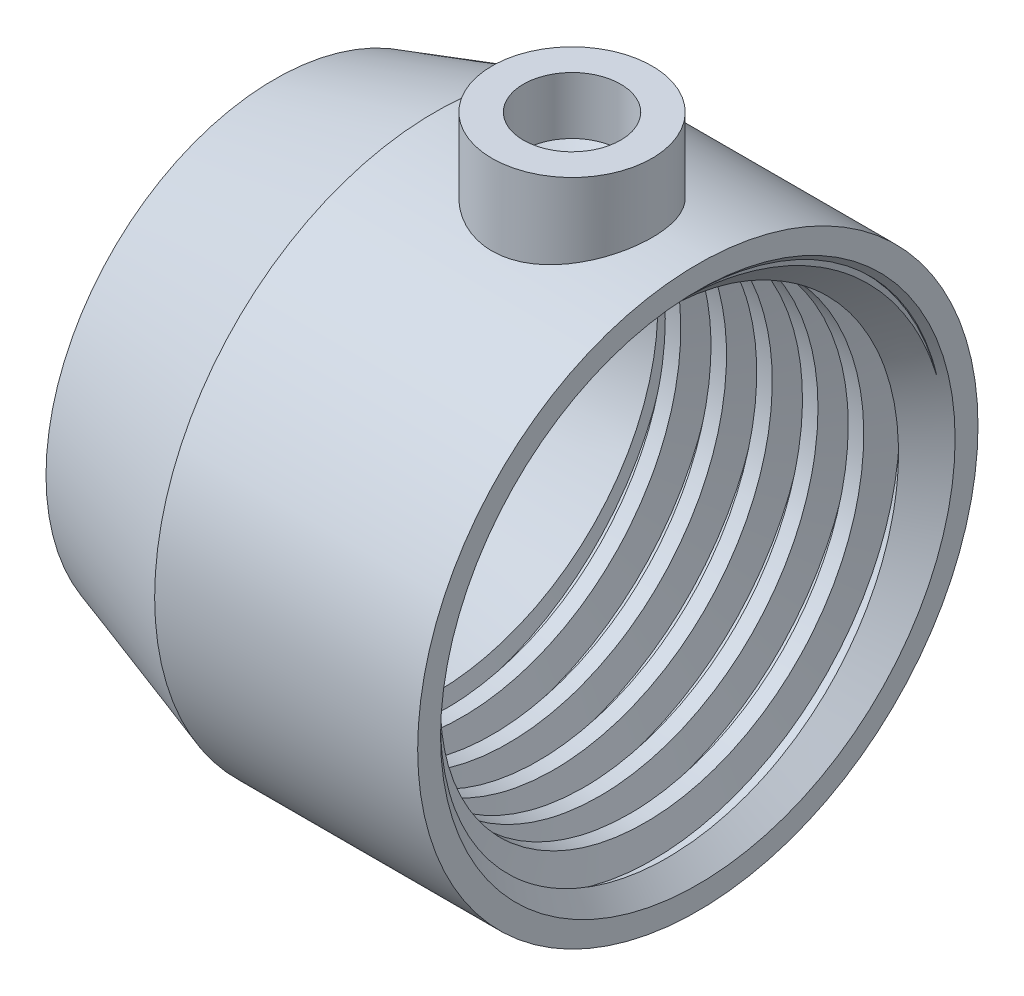
SolidWorks part; units mm, degrees
ref_plane "Front Plane" through (0, 0, 0) normal (0, 0, 1) x (1, 0, 0)
ref_plane "Top Plane" through (0, 0, 0) normal (0, 1, 0) x (1, 0, 0)
ref_plane "Right Plane" through (0, 0, 0) normal (1, 0, 0) x (0, 0, -1)
sketch "Sketch1" plane through (0, 0, 0) normal (0, 0, 1) x (1, 0, 0)
  line L0 (0, 0) -> (39.5756, 0) construction
  line L1 (0, 13.5) -> (0, 20)
  line L2 (0, 20) -> (14, 24.5)
  line L3 (14, 24.5) -> (37, 24.5)
  line L4 (37, 24.5) -> (37, 19.5)
  line L5 (37, 19.5) -> (14, 19.5)
  line L6 (14, 19.5) -> (3, 15.9643)
  line L7 (3, 15.9643) -> (3, 13.5)
  line L8 (3, 13.5) -> (0, 13.5)
  dimension "D1" = 37
  dimension "D2" = 13.5
  dimension "D3" = 19.5
  dimension "D4" = 24.5
  dimension "D5" = 20
  dimension "D6" = 13.5
  dimension "D7" = 3
  dimension "D8" = 11
revolve "Revolve1" add sketch "Sketch1" angle 360 about L0
chamfer "Chamfer1" distance 3 angle 45 1 edges at (37, 0, 19.5)
sketch "Sketch2" plane through (37, 0, 0) normal (1, 0, 0) x (0, 0, -1)
  circle A0 centre (0, 0) radius 19.5 construction
  circle A1 centre (0, 0) radius 19.5
curve "Helix/Spiral1" pitch 4 height 23 turns 5.75
sketch "Sketch4" plane through (0, 0, 0) normal (0, 0, 1) x (1, 0, 0)
  line L0 (37, -19.5) -> (39.6431, -19.5)
  line L1 (37, -24.5) -> (37, 24.5) construction
  line L2 (39.6431, -19.5) -> (38.9965, -22)
  line L3 (38.9965, -22) -> (37.6465, -22)
  line L4 (37.6465, -22) -> (37, -19.5)
  line L5 (38.3215, -19.5) -> (38.3215, -22.5962) construction
  spline S0 degree 3 poles (37, -19.5) (36.9318, -19.5) (36.7945, -18.8178) (36.5893, -15.8533) (36.3839, -11.2534) (36.1786, -5.4927) (35.9732, 0.8346) (35.7679, 7.0758) (35.5625, 12.5871) (35.3571, 16.8) (35.1518, 19.2798) (34.9464, 19.7709) (34.7411, 18.2225) (34.5357, 14.7944) (34.3304, 9.8401) (34.125, 3.8708) (33.9196, -2.4978) (33.7143, -8.6087) (33.5089, -13.8316) (33.3036, -17.6278) (33.0982, -19.6055) (32.8929, -19.5608) (32.6875, -17.4983) (32.4821, -13.6308) (32.2768, -8.3572) (32.0714, -2.2215) (31.8661, 4.1433) (31.6607, 10.0808) (31.4554, 14.9783) (31.25, 18.3308) (31.0446, 19.7924) (30.8393, 19.2122) (30.6339, 16.6503) (30.4286, 12.3707) (30.2232, 6.8151) (30.0179, 0.5565) (29.8125, -5.7596) (29.6071, -11.4815) (29.4018, -16.019) (29.1964, -18.9041) (28.9911, -19.8392) (28.7857, -18.7277) (28.5804, -15.6844) (28.375, -11.0231) (28.1696, -5.2248) (27.9643, 1.1125) (27.7589, 7.335) (27.5536, 12.8009) (27.3482, 16.9463) (27.1429, 19.3437) (26.9375, 19.7456) (26.7321, 18.1106) (26.5268, 14.6075) (26.3214, 9.5975) (26.1161, 3.5975) (25.9107, -2.7736) (25.7054, -8.8586) (25.5, -14.0298) (25.2946, -17.7537) (25.0893, -19.6463) (24.8839, -19.5122) (24.6786, -17.3654) (24.4732, -13.4272) (24.2679, -8.104) (24.0625, -1.9448) (23.8571, 4.4151) (23.6518, 10.3195) (23.4464, 15.1594) (23.2411, 18.4355) (23.0357, 19.8099) (22.8304, 19.1408) (22.625, 16.4973) (22.4196, 12.152) (22.2143, 6.5531) (22.0089, 0.2783) (21.8036, -6.0253) (21.5982, -11.7073) (21.3929, -16.1816) (21.1875, -18.9868) (20.9821, -19.8333) (20.7768, -18.634) (20.5714, -15.5124) (20.3661, -10.7907) (20.1607, -4.9558) (19.9554, 1.3902) (19.75, 7.5929) (19.5446, 13.0123) (19.3393, 17.0894) (19.1339, 19.4037) (18.9286, 19.7164) (18.7232, 17.9952) (18.5179, 14.4178) (18.3125, 9.353) (18.1071, 3.3235) (17.9018, -3.0489) (17.6964, -9.1067) (17.4911, -14.2252) (17.2857, -17.8762) (17.0804, -19.6833) (16.875, -19.4599) (16.6696, -17.2291) (16.4643, -13.2211) (16.2589, -7.8492) (16.0536, -1.6677) (15.8482, 4.6859) (15.6429, 10.5561) (15.4375, 15.3374) (15.2321, 18.5365) (15.0268, 19.8236) (14.8214, 19.0656) (14.6161, 16.3414) (14.4107, 11.9297) (14.2055, 6.294) (14.0682, 2.0877) (14, 0) knots 0 0 0 0 0.008929 0.017857 0.026786 0.035714 0.044643 0.053571 0.0625 0.071429 0.080357 0.089286 0.098214 0.107143 0.116071 0.125 0.133929 0.142857 0.151786 0.160714 0.169643 0.178571 0.1875 0.196429 0.205357 0.214286 0.223214 0.232143 0.241071 0.25 0.258929 0.267857 0.276786 0.285714 0.294643 0.303571 0.3125 0.321429 0.330357 0.339286 0.348214 0.357143 0.366071 0.375 0.383929 0.392857 0.401786 0.410714 0.419643 0.428571 0.4375 0.446429 0.455357 0.464286 0.473214 0.482143 0.491071 0.5 0.508929 0.517857 0.526786 0.535714 0.544643 0.553571 0.5625 0.571429 0.580357 0.589286 0.598214 0.607143 0.616071 0.625 0.633929 0.642857 0.651786 0.660714 0.669643 0.678571 0.6875 0.696429 0.705357 0.714286 0.723214 0.732143 0.741071 0.75 0.758929 0.767857 0.776786 0.785714 0.794643 0.803571 0.8125 0.821429 0.830357 0.839286 0.848214 0.857143 0.866071 0.875 0.883929 0.892857 0.901786 0.910714 0.919643 0.928571 0.9375 0.946429 0.955357 0.964286 0.973214 0.982143 0.991071 1 1 1 1 construction
  dimension "D1" = 2.5
  dimension "D2" = 29
  dimension "D3" = 1.35
sweep "Cut-Sweep1" cut profiles "Sketch4" path "Helix/Spiral1"
ref_plane "Plane1" through (0, 30.5, 0) normal (0, 1, 0) x (1, 0, 0)
sketch "Sketch7" plane through (0, 30.5, 0) normal (0, 1, 0) x (1, 0, 0)
  line L0 (37, -24.5) -> (37, 24.5) construction
  circle A0 centre (26, 0) radius 7
  dimension "D2" = 14
  dimension "D1" = 11
extrude "Boss-Extrude1" add sketch "Sketch7" against normal up to surface (7.0213 mm away)
hole_wizard "M10x1.5 Tapped Hole1" positions "Sketch8" profile "Sketch9" tap size "M10x1.5" standard "ANSI Metric"
sketch "Sketch8" plane through (0, 30.5, 0) normal (0, 1, 0) x (1, 0, 0)
  point P0 (26, 0)
sketch "Sketch9" plane through (26, 30.5, 0) normal (1, 0, 0) x (0, 0, 1)
  line L0 (0, 0) -> (0, 7.5537)
  line L1 (0, 7.5537) -> (4.25, 5)
  line L2 (4.25, 5) -> (4.25, 0)
  line L5 (4.25, 0) -> (0, 0)
  line L10 (0, 7.5537) -> (-4.25, 5) construction
  line L11 (0, -6.35) -> (0, 107.95) construction
  dimension "Tap Drill Dia." = 8.5
  dimension "Tap Drill Depth" = 5
  dimension "Drill Angle" = 118
cosmetic thread "Hole Thread1" parameters "D1"=3.5, "D2"=10
